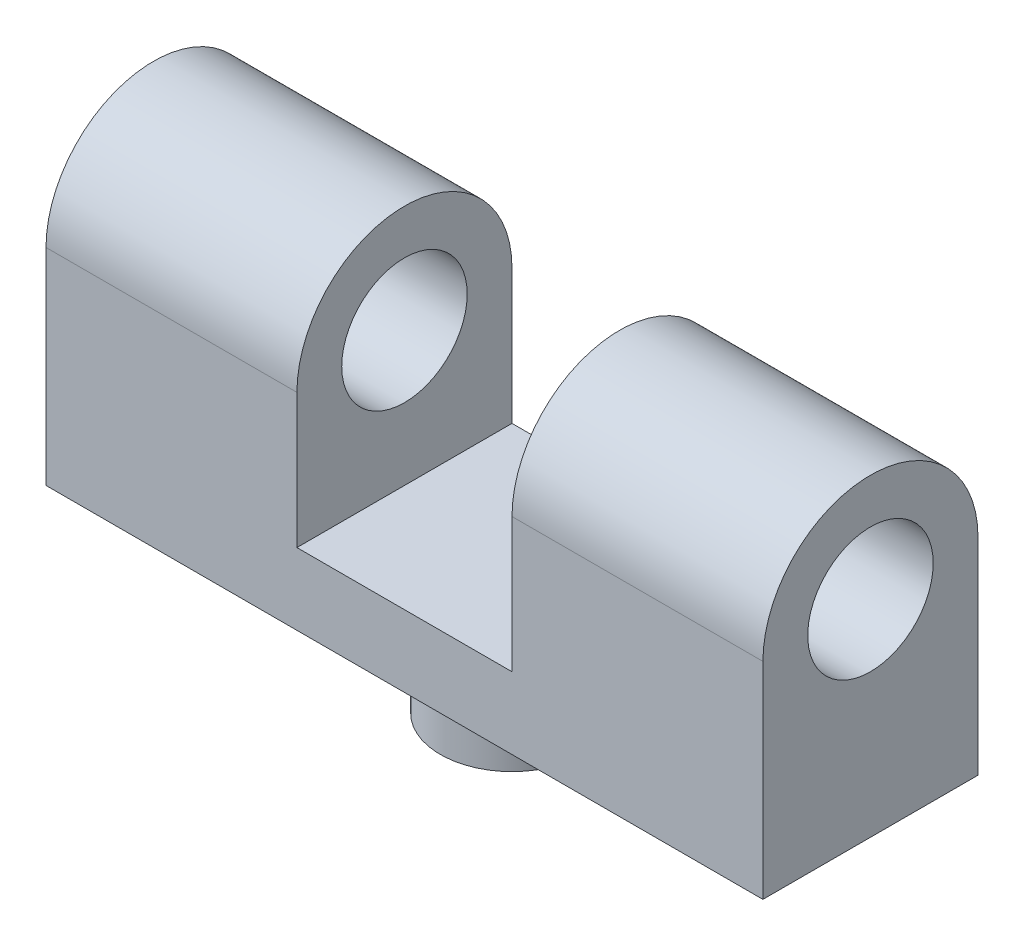
SolidWorks part; units mm, degrees
ref_plane "Plano frontal" through (0, 0, 0) normal (0, 0, 1) x (1, 0, 0)
ref_plane "Plano superior" through (0, 0, 0) normal (0, 1, 0) x (1, 0, 0)
ref_plane "Plano direito" through (0, 0, 0) normal (1, 0, 0) x (0, 0, -1)
sketch "Esboço3" plane through (0, 0, 0) normal (0, 1, 0) x (1, 0, 0)
  circle A1 centre (0, 0) radius 15
  dimension "D2" = 30
extrude "Ressalto-extrusão2" add sketch "Esboço3" along normal blind 20
sketch "Esboço5" plane through (0, 0, 0) normal (1, 0, 0) x (0, 0, -1)
  line L0 (0, 20) -> (0, 28.75) construction
  line L1 (15, 20) -> (-15, 20) construction
  circle A0 centre (0, 28.75) radius 15
  circle A1 centre (0, 28.75) radius 8.75
  dimension "D2" = 17.5
  dimension "D3" = 30
extrude "Ressalto-extrusão3" add sketch "Esboço5" along normal blind 50 and the other way blind 50 separate body
sketch "Esboço6" plane through (0, 0, 0) normal (0, 1, 0) x (1, 0, 0)
  line L0 (50, 15) -> (-50, 15) construction
  line L1 (-15, 15) -> (15, 15)
  line L2 (-15, 15) -> (-15, -15)
  line L3 (-15, -15) -> (15, -15)
  line L4 (15, 15) -> (15, -15)
  line L5 (-15, 15) -> (15, -15) construction
  line L6 (-15, -15) -> (15, 15) construction
  point P0 (0, 0)
  dimension "D2" = 30
extrude "Corte-extrusão2" cut sketch "Esboço6" along normal through all from surface starting at face at (0, 20, 15)
sketch "Esboço7" plane through (0, 0, 0) normal (0, -1, 0) x (1, 0, 0)
  line L0 (50, -15) -> (50, 15) construction
  line L1 (-50, 15) -> (50, 15)
  line L2 (-50, 15) -> (-50, -15)
  line L3 (-50, -15) -> (50, -15)
  line L4 (50, 15) -> (50, -15)
extrude "Ressalto-extrusão4" add sketch "Esboço7" against normal up to surface (28.75 mm away) up to face at (0, 31.875, 0)
sketch "Esboço8" plane through (0, 20, 0) normal (0, 1, 0) x (1, 0, 0)
  line L1 (-15, 15) -> (15, 15)
  line L2 (-15, 15) -> (-15, -15)
  line L3 (-15, -15) -> (15, -15)
  line L4 (15, 15) -> (15, -15)
extrude "Corte-extrusão3" cut sketch "Esboço8" along normal through all and the other way blind 10
sketch "Esboço9" plane through (0, 0, 0) normal (0, -1, 0) x (1, 0, 0)
  circle A0 centre (0, 0) radius 10
  dimension "D1" = 20
extrude "Ressalto-extrusão5" add sketch "Esboço9" along normal blind 10
